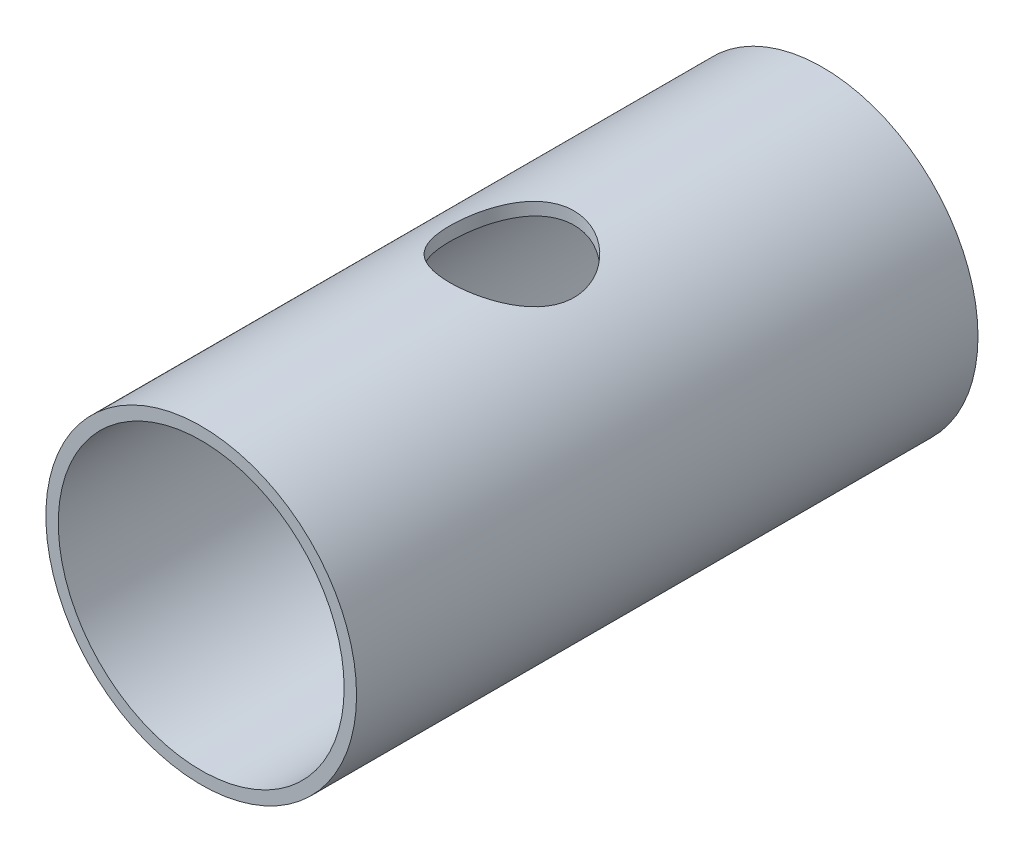
SolidWorks part; units mm, degrees
ref_plane "Front Plane" through (0, 0, 0) normal (0, 0, 1) x (1, 0, 0)
ref_plane "Top Plane" through (0, 0, 0) normal (0, 1, 0) x (1, 0, 0)
ref_plane "Right Plane" through (0, 0, 0) normal (1, 0, 0) x (0, 0, -1)
sketch "Sketch1" plane through (0, 0, 0) normal (0, 0, 1) x (1, 0, 0)
  circle A0 centre (0, 0) radius 11.5
  circle A1 centre (0, 0) radius 12.5
  dimension "D1" = 25
  dimension "D2" = 23
extrude "Boss-Extrude1" add sketch "Sketch1" along normal blind 50
sketch "Sketch2" plane through (0, 0, 0) normal (0, 1, 0) x (1, 0, 0)
  line L0 (0, 0) -> (0, -50) construction
  line L1 (-12.5, -50) -> (12.5, -50) construction
  circle A0 centre (0, -25) radius 5
extrude "Cut-Extrude1" cut sketch "Sketch2" against normal through all both and the other way through all
